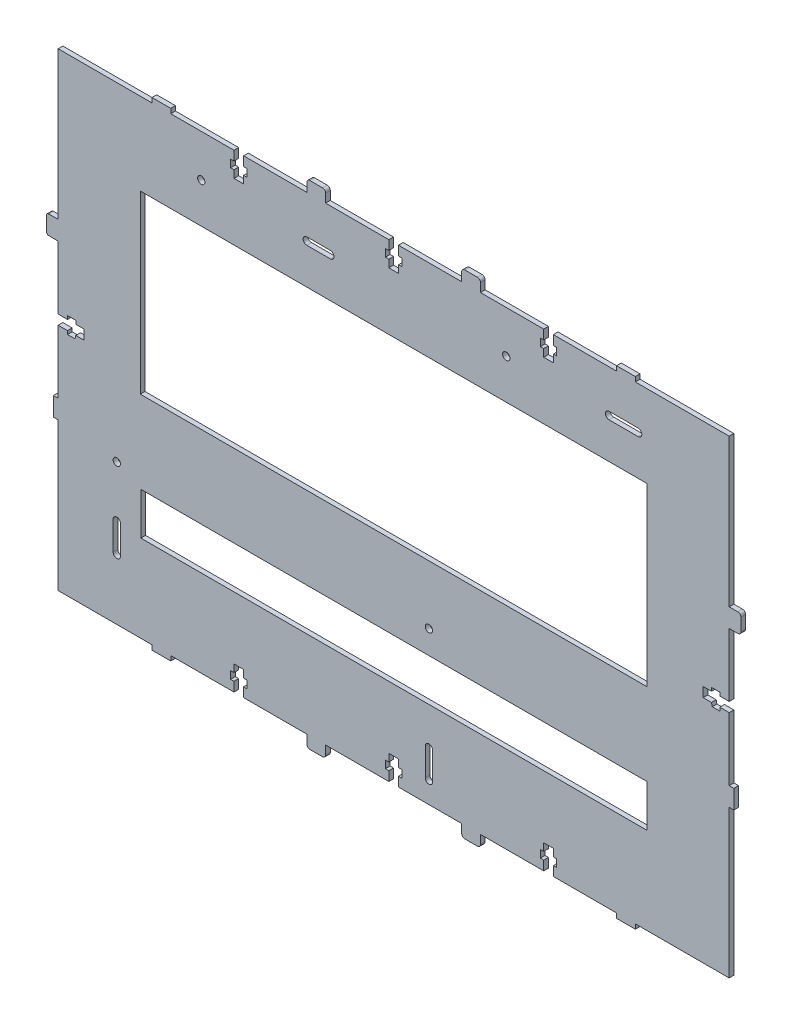
SolidWorks part; units mm, degrees
ref_plane "前视基准面" through (0, 0, 0) normal (0, 0, 1) x (1, 0, 0)
ref_plane "上视基准面" through (0, 0, 0) normal (0, 1, 0) x (1, 0, 0)
ref_plane "右视基准面" through (0, 0, 0) normal (1, 0, 0) x (0, 0, -1)
sketch "草图1" plane through (0, 0, 0) normal (0, 0, 1) x (1, 0, 0)
  line L0 (0, 0) -> (0, -4)
  line L1 (0, -4) -> (-1.45, -4)
  line L2 (-1.45, -4) -> (-1.45, -7.2)
  line L3 (-1.45, -7.2) -> (0, -7.2)
  line L4 (0, -7.2) -> (0, -10.4)
  line L5 (0, -10.4) -> (4.1, -10.4)
  line L6 (4.1, -10.4) -> (4.1, -7.2)
  line L7 (4.1, -7.2) -> (5.55, -7.2)
  line L8 (5.55, -7.2) -> (5.55, -4)
  line L9 (5.55, -4) -> (4.1, -4)
  line L10 (4.1, -4) -> (4.1, 0)
  line L11 (0, 0) -> (-26.95, 0)
  line L12 (-26.95, 0) -> (-26.95, 5)
  line L13 (-26.95, 5) -> (-34.95, 5)
  line L14 (-34.95, 5) -> (-34.95, 0)
  line L15 (2.05, -10.4) -> (2.05, -6.664) construction
  line L16 (-30.95, 5) -> (-30.95, -50.064) construction
  line L17 (-67.45, -4) -> (-66, -4)
  line L18 (-66, -7.2) -> (-67.45, -7.2)
  line L19 (-60.45, -7.2) -> (-61.9, -7.2)
  line L20 (-61.9, -4) -> (-60.45, -4)
  line L21 (-66, -4) -> (-66, 0)
  line L22 (-66, -10.4) -> (-66, -7.2)
  line L23 (-61.9, -10.4) -> (-66, -10.4)
  line L24 (-61.9, -7.2) -> (-61.9, -10.4)
  line L25 (-67.45, -7.2) -> (-67.45, -4)
  line L26 (-60.45, -4) -> (-60.45, -7.2)
  line L27 (-61.9, 0) -> (-61.9, -4)
  line L28 (-61.9, 0) -> (-34.95, 0)
  line L29 (31.05, 5) -> (39.05, 5)
  line L30 (31.05, 0) -> (31.05, 5)
  line L31 (39.05, 5) -> (39.05, 0)
  line L32 (4.1, 0) -> (31.05, 0)
  line L33 (66, 0) -> (39.05, 0)
  line L34 (66, 0) -> (66, -4)
  line L35 (64.55, -4) -> (64.55, -7.2)
  line L36 (71.55, -7.2) -> (71.55, -4)
  line L37 (66, -7.2) -> (66, -10.4)
  line L38 (66, -10.4) -> (70.1, -10.4)
  line L39 (70.1, -10.4) -> (70.1, -7.2)
  line L40 (70.1, -4) -> (70.1, 0)
  line L41 (66, -4) -> (64.55, -4)
  line L42 (64.55, -7.2) -> (66, -7.2)
  line L43 (70.1, -7.2) -> (71.55, -7.2)
  line L44 (71.55, -4) -> (70.1, -4)
  line L45 (68.05, -10.4) -> (68.05, -6.536) construction
  line L46 (70.1, 0) -> (97.05, 0)
  line L47 (132, 0) -> (105.05, 0)
  line L48 (97.05, 5) -> (97.05, 0)
  line L49 (105.05, 0) -> (105.05, 5)
  line L50 (105.05, 5) -> (97.05, 5)
  line L51 (-63.95, -10.4) -> (-63.95, -6.536) construction
  line L52 (-96.95, 5) -> (-96.95, -50.064) construction
  line L53 (-66, 0) -> (-92.95, 0)
  line L54 (-92.95, 5) -> (-92.95, 0)
  line L55 (-100.95, 5) -> (-92.95, 5)
  line L56 (-100.95, 0) -> (-100.95, 5)
  line L57 (-127.9, 0) -> (-100.95, 0)
  line L58 (2.05, -10.4) -> (-140.5, -10.4) construction
  line L59 (-127.9, 0) -> (-140.95, 0)
  line L60 (132, 0) -> (145.05, 0)
  line L63 (145.05, -200) -> (145.05, 0) construction
  line L64 (145.05, -100) -> (115.1583, -100) construction
  line L65 (-127.9, -200) -> (-140.95, -200)
  line L66 (2.05, -189.6) -> (2.05, -193.336) construction
  line L67 (4.1, -196) -> (4.1, -200)
  line L68 (5.55, -196) -> (4.1, -196)
  line L69 (5.55, -192.8) -> (5.55, -196)
  line L70 (4.1, -192.8) -> (5.55, -192.8)
  line L71 (4.1, -189.6) -> (4.1, -192.8)
  line L72 (0, -189.6) -> (4.1, -189.6)
  line L73 (0, -192.8) -> (0, -189.6)
  line L74 (-1.45, -192.8) -> (0, -192.8)
  line L75 (-1.45, -196) -> (-1.45, -192.8)
  line L76 (0, -196) -> (-1.45, -196)
  line L77 (0, -200) -> (0, -196)
  line L78 (132, -200) -> (145.05, -200)
  line L79 (68.05, -189.6) -> (68.05, -193.464) construction
  line L80 (105.05, -205) -> (97.05, -205)
  line L81 (105.05, -200) -> (105.05, -205)
  line L82 (97.05, -205) -> (97.05, -200)
  line L83 (132, -200) -> (105.05, -200)
  line L84 (70.1, -200) -> (97.05, -200)
  line L85 (71.55, -196) -> (70.1, -196)
  line L86 (70.1, -192.8) -> (71.55, -192.8)
  line L87 (64.55, -192.8) -> (66, -192.8)
  line L88 (66, -196) -> (64.55, -196)
  line L89 (70.1, -196) -> (70.1, -200)
  line L90 (70.1, -189.6) -> (70.1, -192.8)
  line L91 (66, -189.6) -> (70.1, -189.6)
  line L92 (66, -192.8) -> (66, -189.6)
  line L93 (71.55, -192.8) -> (71.55, -196)
  line L94 (64.55, -196) -> (64.55, -192.8)
  line L95 (66, -200) -> (66, -196)
  line L96 (66, -200) -> (39.05, -200)
  line L97 (4.1, -200) -> (31.05, -200)
  line L98 (39.05, -205) -> (39.05, -200)
  line L99 (31.05, -200) -> (31.05, -205)
  line L100 (31.05, -205) -> (39.05, -205)
  line L101 (2.05, -189.6) -> (-140.5, -189.6) construction
  line L102 (-96.95, -205) -> (-96.95, -149.936) construction
  line L103 (-63.95, -189.6) -> (-63.95, -193.464) construction
  line L104 (-30.95, -205) -> (-30.95, -149.936) construction
  line L105 (-127.9, -200) -> (-100.95, -200)
  line L106 (-100.95, -200) -> (-100.95, -205)
  line L107 (-100.95, -205) -> (-92.95, -205)
  line L108 (-92.95, -205) -> (-92.95, -200)
  line L109 (-66, -200) -> (-92.95, -200)
  line L110 (-61.9, -200) -> (-34.95, -200)
  line L111 (-61.9, -200) -> (-61.9, -196)
  line L112 (-60.45, -196) -> (-60.45, -192.8)
  line L113 (-67.45, -192.8) -> (-67.45, -196)
  line L114 (-61.9, -192.8) -> (-61.9, -189.6)
  line L115 (-61.9, -189.6) -> (-66, -189.6)
  line L116 (-66, -189.6) -> (-66, -192.8)
  line L117 (-66, -196) -> (-66, -200)
  line L118 (-61.9, -196) -> (-60.45, -196)
  line L119 (-60.45, -192.8) -> (-61.9, -192.8)
  line L120 (-66, -192.8) -> (-67.45, -192.8)
  line L121 (-67.45, -196) -> (-66, -196)
  line L122 (-34.95, -205) -> (-34.95, -200)
  line L123 (-26.95, -205) -> (-34.95, -205)
  line L124 (-26.95, -200) -> (-26.95, -205)
  line L125 (0, -200) -> (-26.95, -200)
  line L126 (145.05, -97.95) -> (141.05, -97.95)
  line L127 (141.05, -97.95) -> (141.05, -96.4903)
  line L128 (141.05, -96.4903) -> (137.5152, -96.4903)
  line L129 (137.5152, -96.4903) -> (137.5152, -97.95)
  line L130 (137.5152, -97.95) -> (133.9804, -97.95)
  line L131 (133.9804, -97.95) -> (133.9804, -102.05)
  line L132 (133.9804, -102.05) -> (137.5152, -102.05)
  line L133 (137.5152, -102.05) -> (137.8502, -103.4708)
  line L134 (137.8502, -103.4708) -> (141.05, -103.5097)
  line L135 (141.05, -103.5097) -> (141.05, -102.05)
  line L136 (141.05, -102.05) -> (145.05, -102.05)
  line L137 (133.9804, -100) -> (145.05, -100) construction
  line L138 (150.05, -67) -> (145.05, -67) construction
  line L139 (145.05, -71) -> (150.05, -71)
  line L140 (150.05, -71) -> (150.05, -63)
  line L141 (150.05, -63) -> (145.05, -63)
  line L142 (150.05, -133) -> (145.05, -133) construction
  line L143 (150.05, -137) -> (145.05, -137)
  line L144 (150.05, -129) -> (150.05, -137)
  line L145 (145.05, -129) -> (150.05, -129)
  line L146 (145.05, -97.95) -> (145.05, -71)
  line L147 (145.05, -102.05) -> (145.05, -129)
  line L148 (145.05, -137) -> (145.05, -200)
  line L149 (145.05, -63) -> (145.05, 0)
  line L150 (-145.95, -133) -> (-140.95, -133) construction
  line L151 (-145.95, -67) -> (-140.95, -67) construction
  line L152 (-140.95, -200) -> (145.05, 0) construction
  line L153 (-115.95, -140) -> (-115.95, -168) construction
  line L154 (-140.95, -102.05) -> (-140.95, -129)
  line L155 (-140.95, -97.95) -> (-140.95, -71)
  line L156 (-140.95, -129) -> (-145.95, -129)
  line L157 (-145.95, -129) -> (-145.95, -137)
  line L158 (-145.95, -137) -> (-140.95, -137)
  line L159 (-145.95, -63) -> (-140.95, -63)
  line L160 (-145.95, -71) -> (-145.95, -63)
  line L161 (-140.95, -71) -> (-145.95, -71)
  line L162 (-136.95, -102.05) -> (-140.95, -102.05)
  line L163 (-136.95, -103.5097) -> (-136.95, -102.05)
  line L164 (-133.7502, -103.4708) -> (-136.95, -103.5097)
  line L165 (-133.4152, -102.05) -> (-133.7502, -103.4708)
  line L166 (-129.8804, -102.05) -> (-133.4152, -102.05)
  line L167 (-129.8804, -97.95) -> (-129.8804, -102.05)
  line L168 (-133.4152, -97.95) -> (-129.8804, -97.95)
  line L169 (-133.4152, -96.4903) -> (-133.4152, -97.95)
  line L170 (-136.95, -96.4903) -> (-133.4152, -96.4903)
  line L171 (-136.95, -97.95) -> (-136.95, -96.4903)
  line L172 (-140.95, -97.95) -> (-136.95, -97.95)
  line L173 (-140.95, 0) -> (-140.95, -63)
  line L174 (-140.95, -200) -> (-140.95, -137)
  line L177 (-115.95, -161.9053) -> (-115.95, -174.0947) construction
  line L186 (-79.95, -18) -> (-29.95, -18) construction
  line L189 (-24.95, -18) -> (-34.95, -18) construction
  line L192 (-24.95, -19.5628) -> (-34.95, -19.5628)
  line L195 (-24.95, -16.4372) -> (-34.95, -16.4372)
  line L204 (50.05, -18) -> (100.05, -18) construction
  line L205 (106.2495, -18) -> (93.8505, -18) construction
  line L206 (106.2495, -19.5651) -> (93.8505, -19.5651)
  line L209 (-140.95, -132) -> (-140.95, -200) construction
  line L210 (-140.95, -200) -> (150.05, -200) construction
  line L211 (106.2495, -16.4349) -> (93.8505, -16.4349)
  line L214 (-115.95, -140) -> (-87.95, -140) construction
  line L217 (-114.4, -161.9053) -> (-114.4, -174.0947)
  line L220 (-117.5, -161.9053) -> (-117.5, -174.0947)
  line L221 (17.0772, -135) -> (17.0772, -185) construction
  line L222 (17.0772, -190.9053) -> (17.0772, -179.0947) construction
  line L223 (15.5272, -190.9053) -> (15.5272, -179.0947)
  line L224 (18.6272, -190.9053) -> (18.6272, -179.0947)
  line L225 (-79.95, -18) -> (-79.95, -118) construction
  line L231 (-105.95, -35) -> (110.05, -35)
  line L232 (-105.95, -35) -> (-105.95, -110)
  line L233 (-105.95, -110) -> (110.05, -110)
  line L234 (110.05, -35) -> (110.05, -110)
  line L235 (-105.6778, -145) -> (110.05, -145)
  line L236 (-105.6778, -145) -> (-105.6778, -163)
  line L237 (-105.6778, -163) -> (110.05, -163)
  line L238 (110.05, -145) -> (110.05, -163)
  circle A34 centre (53.9612, -25.1313) radius 1.55 construction
  circle A35 centre (-124.95, -18) radius 1.55 construction
  circle A38 centre (-79.95, -18) radius 1.55
  arc A39 (-24.95, -19.5628) -> (-24.95, -16.4372) centre (-24.95, -18) ccw
  arc A40 (-34.95, -16.4372) -> (-34.95, -19.5628) centre (-34.95, -18) ccw
  circle A41 centre (50.05, -18) radius 1.55
  circle A42 centre (100.05, -18) radius 1.55 construction
  arc A43 (106.2495, -19.5651) -> (106.2495, -16.4349) centre (106.2495, -18) ccw
  arc A44 (93.8505, -16.4349) -> (93.8505, -19.5651) centre (93.8505, -18) ccw
  circle A48 centre (-115.95, -140) radius 1.55
  arc A51 (-114.4, -161.9053) -> (-117.5, -161.9053) centre (-115.95, -161.9053) ccw
  arc A52 (-117.5, -174.0947) -> (-114.4, -174.0947) centre (-115.95, -174.0947) ccw
  circle A53 centre (17.0772, -135) radius 1.55
  arc A54 (15.5272, -190.9053) -> (18.6272, -190.9053) centre (17.0772, -190.9053) ccw
  arc A55 (18.6272, -179.0947) -> (15.5272, -179.0947) centre (17.0772, -179.0947) ccw
  point P193 (-115.95, -168)
  point P203 (-29.95, -18)
  point P214 (100.05, -18)
  point P227 (17.0772, -185)
  dimension "D15" = 45
  dimension "D18" = 175
  dimension "D19" = 50
  dimension "D21" = 50
  dimension "D22" = 28
  dimension "D23" = 25
  dimension "D24" = 60
  dimension "D25" = 65
  dimension "D27" = 35
  dimension "D28" = 35
  dimension "D2" = 18
  dimension "D12" = 3.1
  dimension "D1" = 4.1
  dimension "D3" = 4
  dimension "D4" = 3.2
  dimension "D5" = 16
  dimension "D6" = 200
  dimension "D7" = 5
  dimension "D8" = 286
  dimension "D9" = 4.1
  dimension "D10" = 4
  dimension "D11" = 3.2
  dimension "D13" = 8
  dimension "D14" = 5
  dimension "D16" = 33
  dimension "D17" = 8
  dimension "D20" = 50
  dimension "D26" = 35
  dimension "D30" = 35
  dimension "D31" = 18
  dimension "D29" = 75
extrude "凸台-拉伸1" add sketch "草图1" along normal blind 2
sketch "草图2" plane through (0, -200, 0) normal (0, -1, 0) x (1, 0, 0)
  line L0 (0, 1) -> (4.1, 1)
  line L1 (0, 2) -> (0, 0) construction
  line L2 (4.1, 2) -> (4.1, 0) construction
  circle A0 centre (2.05, 1) radius 2.05
sketch "草图3" plane through (0, 0, 0) normal (0, 1, 0) x (1, 0, 0)
  line L0 (0, -1) -> (4.1, -1)
  line L1 (0, -2) -> (0, 0) construction
  line L2 (4.1, -2) -> (4.1, 0) construction
  circle A0 centre (2.05, -1) radius 2.05
fillet "圆角1" radius 1 4 edges at (-145.95, -137, 1) (-145.95, -129, 1) (-145.95, -63, 1) (-145.95, -71, 1)
fillet "圆角2" radius 1.3 20 edges at (97.05, 5, 1) (105.05, 5, 1) (39.05, 5, 1) (31.05, 5, 1) (-26.95, 5, 1) (-34.95, 5, 1) (-100.95, 5, 1) (-92.95, 5, 1) (-100.95, -205, 1) (-92.95, -205, 1) (-34.95, -205, 1) (-26.95, -205, 1) (31.05, -205, 1) (39.05, -205, 1) (97.05, -205, 1) (105.05, -205, 1) (150.05, -137, 1) (150.05, -129, 1) (150.05, -63, 1) (150.05, -71, 1)
sketch "草图4" plane through (0, 0, 2) normal (0, 0, 1) x (1, 0, 0)
  line L0 (-66, 0) -> (-92.95, 0) construction
  line L1 (-103.3854, 10.2629) -> (-87.2942, 10.2629)
  line L2 (-103.3854, 10.2629) -> (-103.3854, 2)
  line L3 (-103.3854, 2) -> (-87.2942, 2)
  line L4 (-87.2942, 10.2629) -> (-87.2942, 2)
  line L5 (90.8931, 10.2629) -> (110.825, 10.2629)
  line L6 (90.8931, 10.2629) -> (90.8931, 2)
  line L7 (90.8931, 2) -> (110.825, 2)
  line L8 (110.825, 10.2629) -> (110.825, 2)
  line L9 (-104.6148, -202) -> (-90.1272, -202)
  line L10 (-104.6148, -202) -> (-104.6148, -207.89)
  line L11 (-104.6148, -207.89) -> (-90.1272, -207.89)
  line L12 (-90.1272, -202) -> (-90.1272, -207.89)
  line L13 (94.1099, -202) -> (110.825, -202)
  line L14 (94.1099, -202) -> (94.1099, -210.1778)
  line L15 (94.1099, -210.1778) -> (110.825, -210.1778)
  line L16 (110.825, -202) -> (110.825, -210.1778)
  line L17 (145.05, 0) -> (105.05, 0) construction
  line L18 (-66, -200) -> (-92.95, -200) construction
  line L19 (105.05, -200) -> (145.05, -200) construction
  line L20 (-140.95, 0) -> (-140.95, -63) construction
  line L21 (-153.0557, -111.648) -> (-142.95, -111.648)
  line L22 (-153.0557, -111.648) -> (-153.0557, -137.7144)
  line L23 (-153.0557, -137.7144) -> (-142.95, -137.7144)
  line L24 (-142.95, -111.648) -> (-142.95, -137.7144)
  line L25 (147.05, -113.9361) -> (152.7115, -113.9361)
  line L26 (147.05, -113.9361) -> (147.05, -141.3929)
  line L27 (147.05, -141.3929) -> (152.7115, -141.3929)
  line L28 (152.7115, -113.9361) -> (152.7115, -141.3929)
  line L29 (145.05, -63) -> (145.05, 0) construction
  dimension "D1" = 2
  dimension "D2" = 2
  dimension "D3" = 2
  dimension "D4" = 2
  dimension "D5" = 2
  dimension "D6" = 2
extrude "切除-拉伸1" cut sketch "草图4" against normal blind 2
